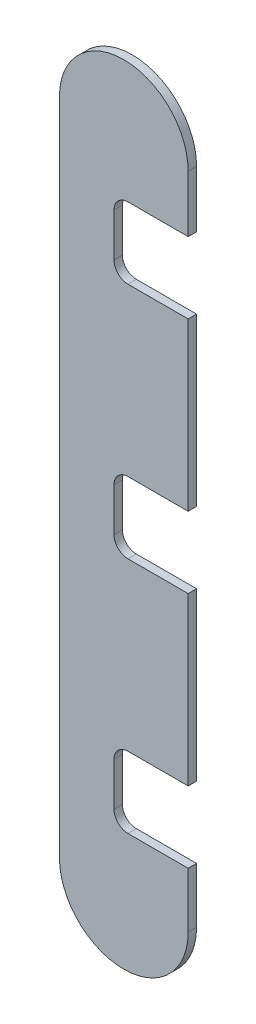
SolidWorks part; units mm, degrees
ref_plane "Front Plane" through (0, 0, 0) normal (0, 0, 1) x (1, 0, 0)
ref_plane "Top Plane" through (0, 0, 0) normal (0, 1, 0) x (1, 0, 0)
ref_plane "Right Plane" through (0, 0, 0) normal (1, 0, 0) x (0, 0, -1)
sketch "Sketch1" plane through (0, 0, 0) normal (0, 0, 1) x (1, 0, 0)
  line L0 (-23.5, 139.9624) -> (-23.5, 114.5)
  line L1 (-43, 160.25) -> (-43, -75.25)
  line L2 (3, 160.25) -> (3, 139.9624)
  line L4 (-23.5, -30.0376) -> (3, -30.0376)
  line L6 (-23.5, -55.5) -> (3, -55.5)
  line L8 (-23.5, 54.9624) -> (3, 54.9624)
  line L10 (-23.5, 29.5) -> (3, 29.5)
  line L12 (-23.5, 139.9624) -> (3, 139.9624)
  line L14 (-23.5, 114.5) -> (3, 114.5)
  line L16 (-23.5, 54.9624) -> (-23.5, 29.5)
  line L17 (-23.5, -30.0376) -> (-23.5, -55.5)
  line L24 (3, -55.5) -> (3, -75.25)
  line L25 (3, 29.5) -> (3, -30.0376)
  line L26 (3, 114.5) -> (3, 54.9624)
  arc A2 (3, 160.25) -> (-43, 160.25) centre (-20, 160.25) ccw
  arc A3 (-43, -75.25) -> (3, -75.25) centre (-20, -75.25) ccw
extrude "Boss-Extrude1" add sketch "Sketch1" along normal blind 3
fillet "Fillet1" radius 5 6 edges at (-23.5, 139.9624, 1.5) (-23.5, 114.5, 1.5) (-23.5, 54.9624, 1.5) (-23.5, 29.5, 1.5) (-23.5, -55.5, 1.5) (-23.5, -30.0376, 1.5)
